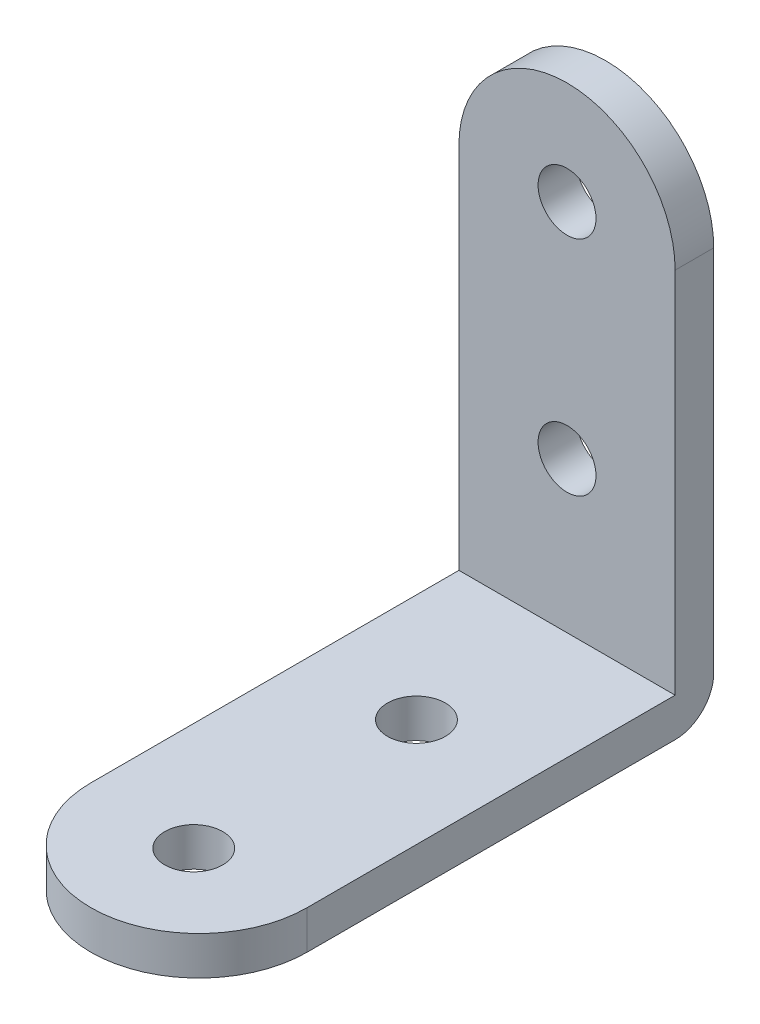
SolidWorks part; units mm, degrees
ref_plane "Front Plane" through (0, 0, 0) normal (0, 0, 1) x (1, 0, 0)
ref_plane "Top Plane" through (0, 0, 0) normal (0, 1, 0) x (1, 0, 0)
ref_plane "Right Plane" through (0, 0, 0) normal (1, 0, 0) x (0, 0, -1)
sketch "Sketch1" plane through (0, 0, 0) normal (0, 0, 1) x (1, 0, 0)
  line L0 (-8.4, 15.8) -> (8.4, 15.8) construction
  line L2 (-8.4, 15.8) -> (-8.4, -15.8)
  line L3 (-8.4, -15.8) -> (8.4, -15.8)
  line L4 (8.4, 15.8) -> (8.4, -15.8)
  line L5 (-8.4, 15.8) -> (8.4, -15.8) construction
  line L6 (-8.4, -15.8) -> (8.4, 15.8) construction
  arc A0 (-8.4, 15.8) -> (8.4, 15.8) centre (0, 15.8) cw
  circle A1 centre (0, 16.2) radius 2.25
  circle A2 centre (0, -1.1) radius 2.25
  point P0 (0, 0)
  dimension "D1" = 4.5
  dimension "D2" = 4.5
  dimension "D6" = 0.4
  dimension "D3" = 31.6
  dimension "D4" = 16.8
  dimension "D5" = 17.3
extrude "Boss-Extrude1" add sketch "Sketch1" along normal blind 3
ref_plane "Plane1" through (0, 0, 1.5) normal (0, 0, 1) x (1, 0, 0)
ref_plane "Plane2" through (0, -14.3, 0) normal (0, -1, 0) x (-1, 0, 0)
ref_axis "Axis1" through (-9.24, -14.3, 1.5) along (1, 0, 0)
pattern_circular "CirPattern1" count 2 every 90 about axis through (-9.24, -14.3, 1.5) along (1, 0, 0) of "Boss-Extrude1"
fillet "Fillet1" radius 3 1 edges at (0, -15.8, 0)
